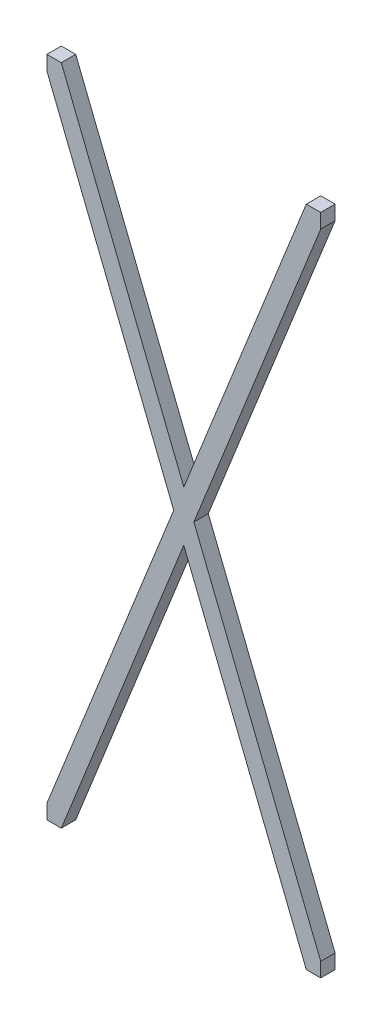
SolidWorks part; units mm, degrees
ref_plane "Ebene vorne" through (0, 0, 0) normal (0, 0, 1) x (1, 0, 0)
ref_plane "Ebene oben" through (0, 0, 0) normal (0, 1, 0) x (1, 0, 0)
ref_plane "Ebene rechts" through (0, 0, 0) normal (1, 0, 0) x (0, 0, -1)
sketch "Skizze1" plane through (0, 0, 0) normal (0, 0, 1) x (1, 0, 0)
  line L0 (0, 2300) -> (50, 2300)
  line L1 (0, 0) -> (50, 0)
  line L2 (0, 0) -> (0, 50)
  line L5 (50, 2300) -> (475, 1237.5)
  line L6 (950, 50) -> (950, 0)
  line L7 (900, 0) -> (475, 1062.5)
  line L8 (0, 2250) -> (0, 2300)
  line L9 (950, 2300) -> (900, 2300)
  line L10 (900, 2300) -> (475, 1237.5)
  line L12 (50, 0) -> (475, 1062.5)
  line L13 (950, 2250) -> (950, 2300)
  line L14 (440, 1150) -> (0, 50)
  line L15 (510, 1150) -> (950, 50)
  line L18 (900, 0) -> (950, 0)
  line L19 (440, 1150) -> (0, 2250)
  line L20 (510, 1150) -> (950, 2250)
  dimension "D1" = 950
  dimension "D2" = 2300
  dimension "D3" = 50
  dimension "D4" = 50
  dimension "D5" = 50
  dimension "D6" = 50
  dimension "D7" = 50
  dimension "D8" = 50
  dimension "D9" = 50
  dimension "D10" = 50
extrude "Aufsatz-Linear austragen1" add sketch "Skizze1" along normal blind 50
